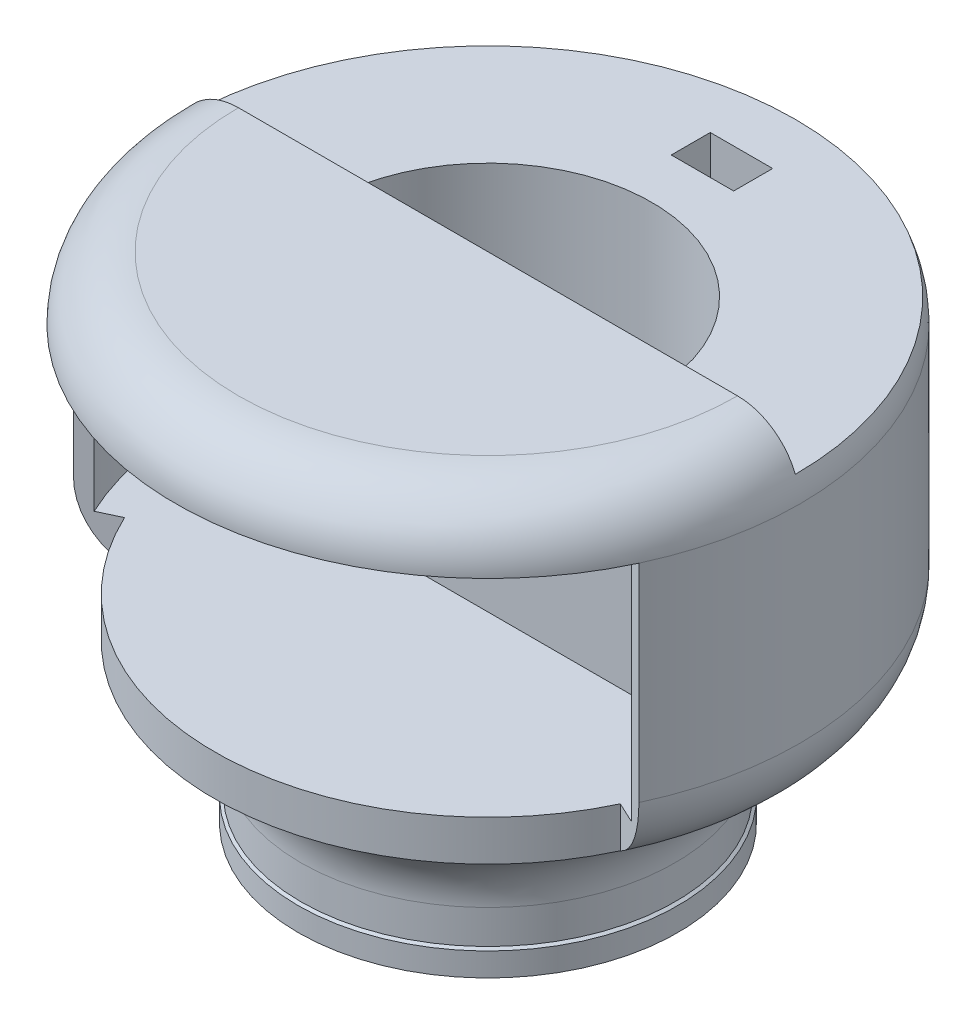
SolidWorks part; units mm, degrees
ref_plane "Front Plane" through (0, 0, 0) normal (0, 0, 1) x (1, 0, 0)
ref_plane "Top Plane" through (0, 0, 0) normal (0, 1, 0) x (1, 0, 0)
ref_plane "Right Plane" through (0, 0, 0) normal (1, 0, 0) x (0, 0, -1)
sketch "Sketch1" plane through (0, 0, 0) normal (0, 0, 1) x (1, 0, 0)
  line L0 (0, 0) -> (0, 90.2242) construction
  line L28 (0, 63.4279) -> (32, 63.4279)
  line L29 (40, 55.4279) -> (40, 28.8468)
  line L30 (22.5, 0) -> (24.35, 0)
  line L31 (24.35, 0) -> (24.35, 3)
  line L32 (24.35, 3) -> (24, 3.25)
  line L33 (24, 3.25) -> (24, 7.5811)
  line L34 (28.5399, 15.9588) -> (35.4601, 20.4691)
  line L35 (0, 13) -> (22, 13)
  line L36 (22.5, 12.5) -> (22.5, 0)
  line L37 (0, 13) -> (0, 63.4279)
  arc A0 (22, 13) -> (22.5, 12.5) centre (22, 12.5) cw
  arc A1 (24, 7.5811) -> (28.5399, 15.9588) centre (34, 7.5811) cw
  arc A2 (35.4601, 20.4691) -> (40, 28.8468) centre (30, 28.8468) ccw
  arc A3 (32, 63.4279) -> (40, 55.4279) centre (32, 55.4279) cw
  point P11 (22.9, 63.4279)
  point P18 (22.5, 13)
  point P21 (24, 13)
  point P24 (40, 23.4279)
  point P27 (40, 63.4279)
  point P28 (28.5604, 23.4279)
  point P31 (22.5, 17)
  dimension "D8" = 9.75
  dimension "D9" = 0.5
  dimension "D4" = 1.85
  dimension "D1" = 22.5
  dimension "D10" = 10
  dimension "D11" = 10
  dimension "D12" = 8
  dimension "D2" = 40
  dimension "D3" = 40
  dimension "D5" = 1.5
  dimension "D6" = 3
  dimension "D7" = 13
revolve "Revolve1" add sketch "Sketch1" angle 360 about L0
ref_plane "Plane1" through (0, 13, 0) normal (0, -1, 0) x (-1, 0, 0)
sketch "Sketch18" plane through (0, 0, 0) normal (0, 0, 1) x (1, 0, 0)
  line L0 (0, 0) -> (0, 101.5813) construction
  line L1 (-24.35, 0) -> (24.35, 0) construction
sketch "Sketch3" plane through (0, 0, 0) normal (0, 0, 1) x (1, 0, 0)
  point P0 (1.2404, 19.1989)
ref_point "Point1"
ref_plane "Plane2" through (0, 0, 22.9) normal (0, 0, 1) x (1, 0, 0)
ref_plane "Plane3" through (0, 0, 40) normal (0, 0, 1) x (1, 0, 0)
ref_plane "Plane4" through (0, 55.4279, 0) normal (0, 1, 0) x (1, 0, 0)
sketch "Sketch9" plane through (0, 55.4279, 0) normal (0, 1, 0) x (1, 0, 0)
  circle A7 centre (0, 0) radius 38
  circle A8 centre (0, 0) radius 40 construction
  circle A9 centre (0, 0) radius 23
  dimension "D1" = 2
  dimension "D2" = 46
ref_plane "Plane5" through (0, 13, 0) normal (0, -1, 0) x (-1, 0, 0)
sketch "Sketch11" plane through (0, 13, 0) normal (0, -1, 0) x (-1, 0, 0)
  line L0 (-21, 0) -> (21, 0)
  arc A1 (-21, 0) -> (21, 0) centre (0, 0) cw
  dimension "D1" = 42
extrude "Cut-Extrude3" cut sketch "Sketch11" against normal blind 60
ref_plane "Plane6" through (0, 0, -40) normal (0, 0, -1) x (-1, 0, 0)
extrude "Cut-Extrude5" cut sketch "Sketch9" against normal blind 30 and the other way blind 2
sketch "Sketch19" plane through (0, 0, 0) normal (1, 0, 0) x (0, 0, -1)
  line L0 (-47.0647, 55.4279) -> (-35.0647, 55.4279)
  line L1 (31.2976, 55.4279) -> (-31.2976, 55.4279) construction
  line L2 (-35.0647, 55.4279) -> (-35.0647, 18.9279)
  line L3 (-35.0647, 18.9279) -> (-47.0647, 18.9279)
  line L4 (-47.0647, 18.9279) -> (-47.0647, 55.4279)
  dimension "D1" = 12
  dimension "D2" = 36.5
revolve "Cut-Revolve2" cut sketch "Sketch19" angle 65 about L0 other way angle 65
ref_plane "Plane7" through (0, 0, 22.5) normal (0, 0, -1) x (-1, 0, 0)
sketch "Sketch21" plane through (0, 0, 22.5) normal (0, 0, -1) x (-1, 0, 0)
  line L0 (0, 0) -> (0, 101.5813) construction
  line L1 (-1.625, 4) -> (1.625, 4)
  line L2 (-1.625, 4) -> (-1.625, 0)
  line L3 (-1.625, 0) -> (1.625, 0)
  line L4 (1.625, 4) -> (1.625, 0)
  line L5 (-1.625, 4) -> (1.625, 0) construction
  line L6 (-1.625, 0) -> (1.625, 4) construction
  line L7 (-22.5, 0) -> (22.5, 0) construction
  point P0 (0, 2)
  dimension "D1" = 4
  dimension "D2" = 3.25
extrude "Boss-Extrude3" add sketch "Sketch21" along normal blind 1.35
pattern_circular "CirPattern1" count 5 over 360 about axis through (0, 0, 0) along (0, -1, 0) of "Boss-Extrude3"
ref_plane "Plane8" through (0, 20.4691, 0) normal (0, 1, 0) x (1, 0, 0)
sketch "Sketch22" plane through (0, 63.4279, 0) normal (0, 1, 0) x (1, 0, 0)
  line L0 (-40, 0) -> (40, 0)
  arc A0 (-40, 0) -> (40, 0) centre (0, 0) cw
  arc A1 (36.2523, -16.9047) -> (-36.2523, -16.9047) centre (0, 0) ccw construction
extrude "Cut-Extrude9" cut sketch "Sketch22" against normal blind 5
sketch "Sketch23" plane through (0, 0, -40) normal (0, 0, -1) x (-1, 0, 0)
  line L0 (0, 0) -> (0, 101.5813) construction
  line L1 (31.2976, 55.4279) -> (-31.2976, 55.4279) construction
  circle A0 centre (0, 42.1379) radius 10.5
  dimension "D1" = 21
  dimension "D2" = 13.29
extrude "Cut-Extrude10" cut sketch "Sketch23" against normal blind 10
sketch "Sketch24" plane through (0, 58.4279, 0) normal (0, 1, 0) x (1, 0, 0)
  line L1 (-7.5, 34) -> (7.5, 34)
  line L2 (-7.5, 34) -> (-7.5, 26)
  line L3 (-7.5, 26) -> (7.5, 26)
  line L4 (7.5, 34) -> (7.5, 26)
  line L5 (-7.5, 34) -> (7.5, 26) construction
  line L6 (-7.5, 26) -> (7.5, 34) construction
  arc A0 (39.4162, 0) -> (-39.4162, 0) centre (0, 0) ccw construction
  point P0 (0, 30)
  dimension "D1" = 30
  dimension "D2" = 8
  dimension "D3" = 15
extrude "Boss-Extrude4" add sketch "Sketch24" against normal blind 8
sketch "Sketch26" plane through (0, 58.4279, 0) normal (0, 1, 0) x (1, 0, 0)
  line L1 (-4, 32.5) -> (4, 32.5)
  line L2 (-4, 32.5) -> (-4, 27.5)
  line L3 (-4, 27.5) -> (4, 27.5)
  line L4 (4, 32.5) -> (4, 27.5)
  line L5 (-4, 32.5) -> (4, 27.5) construction
  line L6 (-4, 27.5) -> (4, 32.5) construction
  arc A0 (39.4162, 0) -> (-39.4162, 0) centre (0, 0) ccw construction
  point P0 (0, 30)
  dimension "D1" = 30
  dimension "D2" = 5
  dimension "D3" = 8
extrude "Cut-Extrude11" cut sketch "Sketch26" against normal blind 10
sketch "Sketch27" plane through (7.5, 0, 0) normal (1, 0, 0) x (0, 0, -1)
  line L0 (34, 50.4279) -> (34, 57.4279) construction
  line L1 (28, 56.4279) -> (32, 56.4279)
  line L2 (28, 56.4279) -> (28, 51.4279)
  line L3 (28, 51.4279) -> (32, 51.4279)
  line L4 (32, 56.4279) -> (32, 51.4279)
  line L5 (28, 56.4279) -> (32, 51.4279) construction
  line L6 (28, 51.4279) -> (32, 56.4279) construction
  line L7 (26, 50.4279) -> (26, 57.4279) construction
  line L8 (26, 50.4279) -> (34, 50.4279) construction
  point P0 (30, 53.9279)
  dimension "D1" = 8
  dimension "D2" = 3.5
  dimension "D3" = 5
  dimension "D4" = 4
extrude "Cut-Extrude12" cut sketch "Sketch27" against normal blind 5
ref_plane "Plane9" through (-39.4162, 58.4279, 0) normal (0.375, 0.927, 0) x (0.927, -0.375, 0)
ref_plane "Plane10" through (0, 58.4279, 0) normal (0, 1, 0) x (1, 0, 0)
sketch3d "3DSketch1"
  line L2 (31.7794, 25.4279, 14.819) -> (34.2611, 25.4279, 15.9762)
  line L3 (-34.2611, 25.4279, 15.9762) -> (-31.7794, 25.4279, 14.819)
  line L4 (31.7794, 25.4279, 14.819) -> (34.2611, 25.4279, 15.9762)
  line L5 (-34.2611, 25.4279, 15.9762) -> (-31.7794, 25.4279, 14.819)
  arc A2 (34.2611, 25.4279, 15.9762) -> (-34.2611, 25.4279, 15.9762) centre (0, 25.4279, 2) ccw
  arc A3 (-31.7794, 25.4279, 14.819) -> (31.7794, 25.4279, 14.819) centre (0, 25.4279, 0) ccw
  arc A4 (34.2611, 25.4279, 15.9762) -> (-34.2611, 25.4279, 15.9762) centre (0, 25.4279, 2) ccw
  arc A5 (-31.7794, 25.4279, 14.819) -> (31.7794, 25.4279, 14.819) centre (0, 25.4279, 0) ccw
  point P6 (0, 62.43, 2)
  point P10 (0, 60.4926, 0)
  point P12 (0, 62.43, 2)
  point P13 (0, 60.4926, 0)
  dimension "D1" = 0
sketch "Sketch28" plane through (0, 55.4279, 0) normal (0, 1, 0) x (1, 0, 0)
  line L0 (-22.9129, -2) -> (22.9129, -2)
  arc A0 (-22.9129, -2) -> (22.9129, -2) centre (0, 0) ccw
  dimension "D1" = 46
  dimension "D2" = 2
extrude "Cut-Extrude14" cut sketch "Sketch28" against normal blind 30
